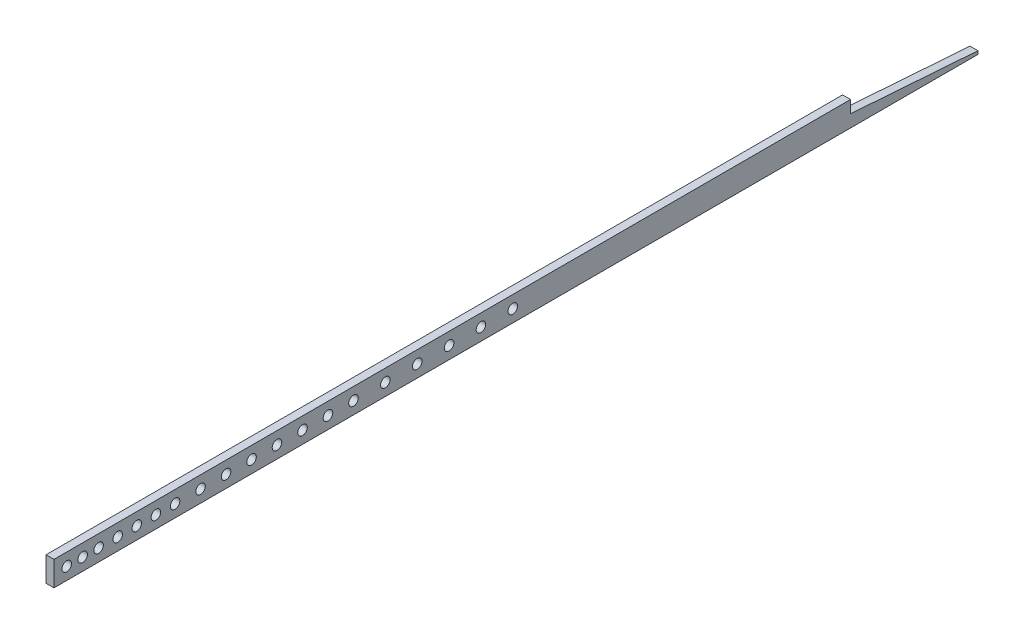
SolidWorks part; units mm, degrees
ref_plane "Ebene vorne" through (0, 0, 0) normal (0, 0, 1) x (1, 0, 0)
ref_plane "Ebene oben" through (0, 0, 0) normal (0, 1, 0) x (1, 0, 0)
ref_plane "Ebene rechts" through (0, 0, 0) normal (1, 0, 0) x (0, 0, -1)
sketch "Skizze1" plane through (0, 0, 0) normal (0, 0, 1) x (1, 0, 0)
  line L1 (0, 0) -> (5, 0)
  line L2 (0, 0) -> (0, 15.5)
  line L3 (0, 15.5) -> (5, 15.5)
  line L4 (5, 0) -> (5, 15.5)
  dimension "D1" = 5
  dimension "D2" = 15.5
extrude "GrundStab" add sketch "Skizze1" along normal blind 500
sketch "Skizze2" plane through (0, 0, 0) normal (-1, 0, 0) x (0, 0, 1)
  line L0 (0, 15.5) -> (0, 7.75)
  line L1 (0, 15.5) -> (0, 0) construction
  line L3 (500, 15.5) -> (0, 15.5) construction
  line L4 (80, 15.5) -> (0, 15.5)
  line L5 (80, 15.5) -> (80, 13.5)
  line L6 (80, 13.5) -> (0, 7.75)
  dimension "D1" = 80
  dimension "D2" = 2
extrude "SchäftungInnen" [suppressed] cut sketch "Skizze2" against normal through all
sketch "Skizze3" plane through (0, 0, 0) normal (-1, 0, 0) x (0, 0, 1)
  line L0 (0, 7.75) -> (-80, 2)
  line L1 (0, 15.5) -> (0, 0) construction
  line L2 (-80, 2) -> (-80, 0)
  line L3 (-80, 0) -> (0, 0)
  line L4 (0, 0) -> (0, 7.75)
  dimension "D1" = 2
  dimension "D2" = 80
extrude "Aufsatz-Linear austragen2" add sketch "Skizze3" against normal through all
sketch "Skizze4" plane through (0, 0, 0) normal (-1, 0, 0) x (0, 0, 1)
  line L0 (500, 7.75) -> (492, 7.75) construction
  line L1 (500, 15.5) -> (500, 0) construction
  circle A0 centre (492, 7.75) radius 3
  circle A1 centre (482, 7.75) radius 3
  circle A2 centre (472, 7.75) radius 3
  circle A3 centre (460, 7.75) radius 3
  circle A4 centre (448, 7.75) radius 3
  circle A5 centre (436, 7.75) radius 3
  circle A6 centre (424, 7.75) radius 3
  circle A7 centre (408, 7.75) radius 3
  circle A8 centre (392, 7.75) radius 3
  circle A9 centre (376, 7.75) radius 3
  circle A10 centre (360, 7.75) radius 3
  circle A11 centre (344, 7.75) radius 3
  circle A12 centre (328, 7.75) radius 3
  circle A13 centre (312, 7.75) radius 3
  circle A14 centre (292, 7.75) radius 3
  circle A15 centre (272, 7.75) radius 3
  circle A16 centre (252, 7.75) radius 3
  circle A17 centre (232, 7.75) radius 3
  circle A18 centre (212, 7.75) radius 3
  dimension "D1" = 6
  dimension "D2" = 8
  dimension "D3" = 3
  dimension "D4" = 5
  dimension "D5" = 8
  dimension "D6" = 6
extrude "Schnitt-Linear austragen1" cut sketch "Skizze4" against normal through all
